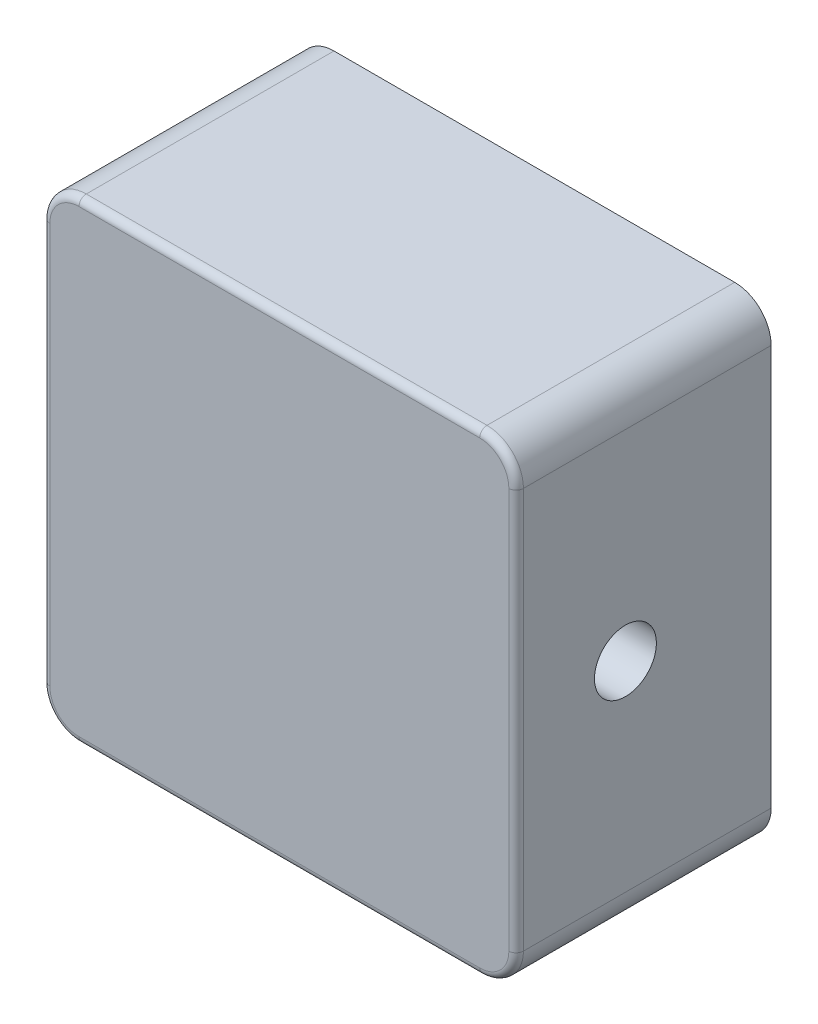
SolidWorks part; units mm, degrees
material "Silicon Rubber"
ref_plane "Front Plane" through (0, 0, 0) normal (0, 0, 1) x (1, 0, 0)
ref_plane "Top Plane" through (0, 0, 0) normal (0, 1, 0) x (1, 0, 0)
ref_plane "Right Plane" through (0, 0, 0) normal (1, 0, 0) x (0, 0, -1)
sketch "Sketch2" plane through (0, 0, 0) normal (0, 0, 1) x (1, 0, 0)
  line L1 (-165.1, -165.1) -> (165.1, -165.1)
  line L2 (-165.1, -165.1) -> (-165.1, 165.1)
  line L3 (-165.1, 165.1) -> (165.1, 165.1)
  line L4 (165.1, -165.1) -> (165.1, 165.1)
  line L5 (-165.1, -165.1) -> (165.1, 165.1) construction
  line L6 (-165.1, 165.1) -> (165.1, -165.1) construction
  point P0 (0, 0)
extrude "Boss-Extrude1" add sketch "Sketch2" along normal blind 177.8
sketch "Sketch3" plane through (165.1, 0, 0) normal (1, 0, 0) x (0, 0, -1)
  circle A0 centre (-101.6, 0) radius 21.59
extrude "Cut-Extrude1" cut sketch "Sketch3" against normal through all both and the other way through all
sketch "Sketch5" plane through (0, 0, 0) normal (0, 0, -1) x (-1, 0, 0)
  circle A0 centre (0, 0) radius 8.382
extrude "Cut-Extrude3" cut sketch "Sketch5" against normal blind 101.6
sketch "Sketch6" plane through (0, -165.1, 0) normal (0, -1, 0) x (1, 0, 0)
  circle A0 centre (0, 101.6) radius 21.59
extrude "Cut-Extrude4" cut sketch "Sketch6" against normal blind 165.1
fillet "Fillet1" radius 5.08 4 edges at (0, -165.1, 177.8) (-165.1, 0, 177.8) (0, 165.1, 177.8) (165.1, 0, 177.8)
fillet "Fillet2" radius 25.4 8 edges at (163.6121, 163.6121, 176.3121) (-163.6121, 163.6121, 176.3121) (-163.6121, -163.6121, 176.3121) (163.6121, -163.6121, 176.3121) (165.1, -165.1, 86.36) (-165.1, -165.1, 86.36) (-165.1, 165.1, 86.36) (165.1, 165.1, 86.36)
